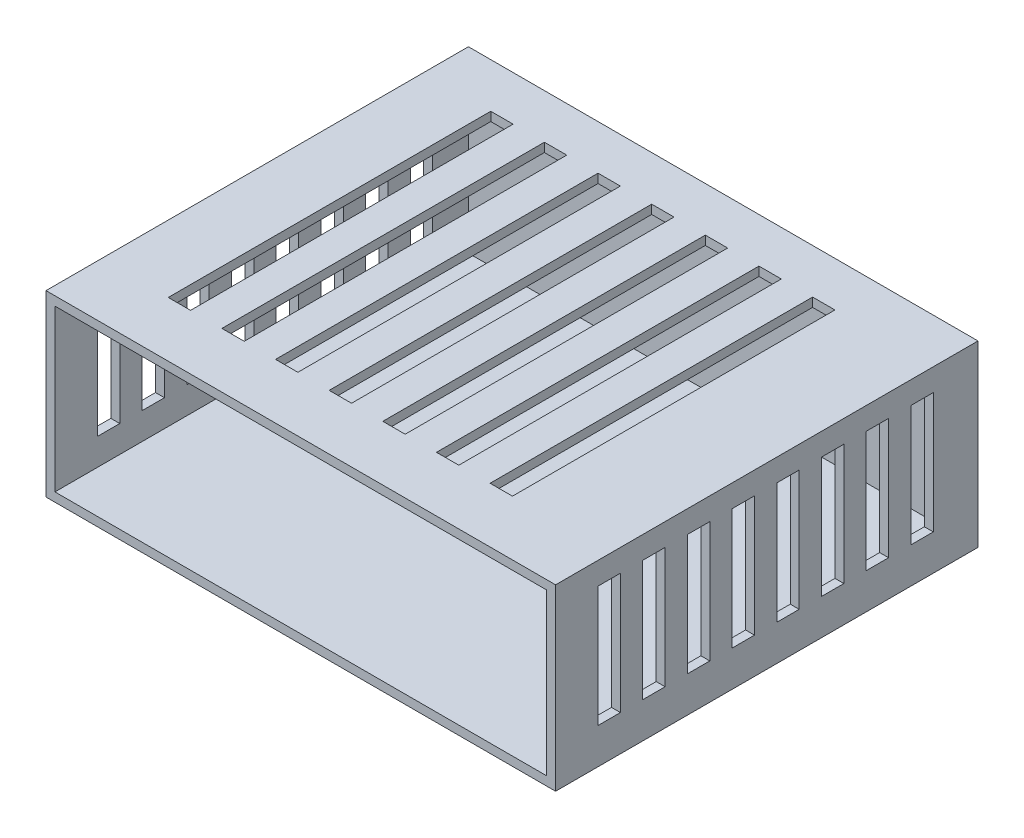
SolidWorks part; units mm, degrees
ref_plane "前视基准面" through (0, 0, 0) normal (0, 0, 1) x (1, 0, 0)
ref_plane "上视基准面" through (0, 0, 0) normal (0, 1, 0) x (1, 0, 0)
ref_plane "右视基准面" through (0, 0, 0) normal (1, 0, 0) x (0, 0, -1)
other "Configuration Table"
sketch "草图1" plane through (0, 0, 0) normal (0, 1, 0) x (1, 0, 0)
  line L1 (0, 0) -> (114, 0)
  line L2 (0, 0) -> (0, 94.5)
  line L3 (0, 94.5) -> (114, 94.5)
  line L4 (114, 0) -> (114, 94.5)
  dimension "D1" = 114
  dimension "D2" = 94.5
extrude "凸台-拉伸1" add sketch "草图1" along normal blind 40
shell "抽壳1" thickness 2 removed face at (57, 20, 0)
sketch "草图2" plane through (0, 40, 0) normal (0, 1, 0) x (1, 0, 0)
  line L0 (0, 94.5) -> (15, 94.5) construction
  line L1 (114, 94.5) -> (0, 94.5) construction
  line L2 (15, 94.5) -> (15, 84.5) construction
  line L6 (15, 84.5) -> (20, 84.5)
  line L7 (15, 84.5) -> (15, 12.3496)
  line L8 (15, 12.3496) -> (20, 12.3496)
  line L9 (20, 84.5) -> (20, 12.3496)
  line L32 (27, 84.5) -> (27, 12.3496)
  line L33 (27, 84.5) -> (32, 84.5)
  line L34 (32, 84.5) -> (32, 12.3496)
  line L35 (27, 12.3496) -> (32, 12.3496)
  line L36 (39, 84.5) -> (39, 12.3496)
  line L37 (39, 84.5) -> (44, 84.5)
  line L38 (44, 84.5) -> (44, 12.3496)
  line L39 (39, 12.3496) -> (44, 12.3496)
  line L40 (51, 84.5) -> (51, 12.3496)
  line L41 (51, 84.5) -> (56, 84.5)
  line L42 (56, 84.5) -> (56, 12.3496)
  line L43 (51, 12.3496) -> (56, 12.3496)
  line L44 (63, 84.5) -> (63, 12.3496)
  line L45 (63, 84.5) -> (68, 84.5)
  line L46 (68, 84.5) -> (68, 12.3496)
  line L47 (63, 12.3496) -> (68, 12.3496)
  line L48 (75, 84.5) -> (75, 12.3496)
  line L49 (75, 84.5) -> (80, 84.5)
  line L50 (80, 84.5) -> (80, 12.3496)
  line L51 (75, 12.3496) -> (80, 12.3496)
  line L52 (87, 84.5) -> (87, 12.3496)
  line L53 (87, 84.5) -> (92, 84.5)
  line L54 (92, 84.5) -> (92, 12.3496)
  line L55 (87, 12.3496) -> (92, 12.3496)
  dimension "D1" = 15
  dimension "D2" = 10
  dimension "D3" = 72.1504
  dimension "D4" = 5
  dimension "D5" = 7
extrude "切除-拉伸3" cut sketch "草图2" against normal blind 20 contours L9 L6 L7 L8 | L35 L34 | L36 L39 L38 L37 | L40 L43 L42 L41 | L44 L47 L46 L45 | L48 L51 L50 L49 | L52 L55 L54 L53 region at (17.5, 40, -48.4248) region at (29.5, 40, -48.4248) region at (41.5, 40, -48.4248) region at (53.5, 40, -48.4248) region at (65.5, 40, -48.4248) region at (77.5, 40, -48.4248) region at (89.5, 40, -48.4248)
sketch "草图6" plane through (0, 0, 0) normal (-1, 0, 0) x (0, 0, 1)
  line L0 (-94.5, 40) -> (-84.5, 40)
  line L1 (-94.5, 40) -> (0, 40) construction
  line L3 (-84.5, 40) -> (-84.5, 35)
  line L5 (-74.5, 35) -> (-74.5, 8)
  line L6 (-84.5, 35) -> (-79.5, 35)
  line L7 (-84.5, 35) -> (-84.5, 8)
  line L8 (-84.5, 8) -> (-79.5, 8)
  line L9 (-79.5, 35) -> (-79.5, 8)
  line L10 (-74.5, 35) -> (-69.5, 35)
  line L11 (-69.5, 35) -> (-69.5, 8)
  line L12 (-74.5, 8) -> (-69.5, 8)
  line L13 (-64.5, 35) -> (-64.5, 8)
  line L14 (-64.5, 35) -> (-59.5, 35)
  line L15 (-59.5, 35) -> (-59.5, 8)
  line L16 (-64.5, 8) -> (-59.5, 8)
  line L17 (-54.5, 35) -> (-54.5, 8)
  line L18 (-54.5, 35) -> (-49.5, 35)
  line L19 (-49.5, 35) -> (-49.5, 8)
  line L20 (-54.5, 8) -> (-49.5, 8)
  line L21 (-44.5, 35) -> (-44.5, 8)
  line L22 (-44.5, 35) -> (-39.5, 35)
  line L23 (-39.5, 35) -> (-39.5, 8)
  line L24 (-44.5, 8) -> (-39.5, 8)
  line L25 (-34.5, 35) -> (-34.5, 8)
  line L26 (-34.5, 35) -> (-29.5, 35)
  line L27 (-29.5, 35) -> (-29.5, 8)
  line L28 (-34.5, 8) -> (-29.5, 8)
  line L29 (-24.5, 35) -> (-24.5, 8)
  line L30 (-24.5, 35) -> (-19.5, 35)
  line L31 (-19.5, 35) -> (-19.5, 8)
  line L32 (-24.5, 8) -> (-19.5, 8)
  line L33 (-14.5, 35) -> (-14.5, 8)
  line L34 (-14.5, 35) -> (-9.5, 35)
  line L35 (-9.5, 35) -> (-9.5, 8)
  line L36 (-14.5, 8) -> (-9.5, 8)
  dimension "D1" = 10
  dimension "D2" = 5
  dimension "D3" = 27
  dimension "D4" = 5
  dimension "D5" = 8
extrude "切除-拉伸4" cut sketch "草图6" against normal blind 1000 contours L9 L6 L7 L8 | L5 L12 L11 L10 | L13 L16 L15 L14 | L17 L20 L19 L18 | L21 L24 L23 L22 | L25 L28 L27 L26 | L29 L32 L31 L30 | L33 L36 L35 L34 region at (0, 21.5, -72) region at (0, 21.5, -82) region at (0, 21.5, -62) region at (0, 21.5, -52) region at (0, 21.5, -42) region at (0, 21.5, -32) region at (0, 21.5, -22) region at (0, 21.5, -12)
